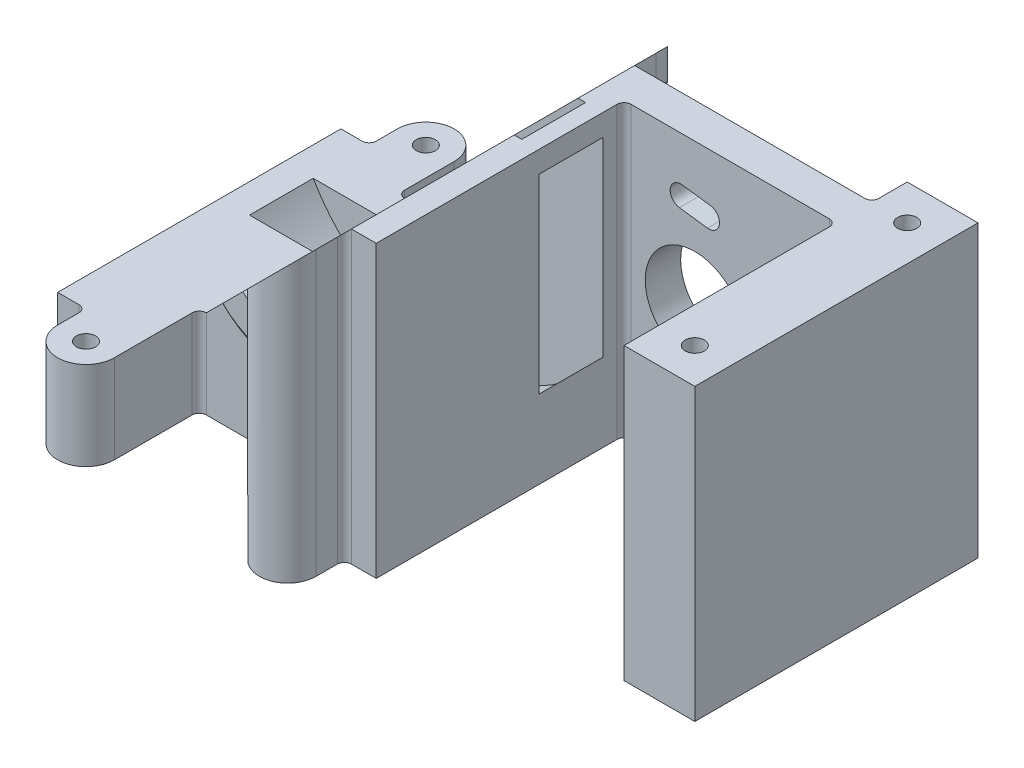
SolidWorks part; units mm, degrees
note: '?' marks a value the reader was unsure of.
ref_plane "Plan de face" through (0, 0, 0) normal (0, 0, 1) x (1, 0, 0)
ref_plane "Plan de dessus" through (0, 0, 0) normal (0, 1, 0) x (1, 0, 0)
ref_plane "Plan de droite" through (0, 0, 0) normal (1, 0, 0) x (0, 0, -1)
sketch "Esquisse1" plane through (0, 0, 0) normal (0, 1, 0) x (1, 0, 0)
  line L0 (-25, 20) -> (20, -20) construction
  line L1 (-30.3181, 0) -> (28.1212, 0) construction
  line L2 (0, 31.6907) -> (0, -43.6751) construction
  line L3 (16.5, 20) -> (49, 20)
  line L4 (15.5, 21) -> (15.5, 24)
  line L5 (7.5, 24) -> (7.5, 17)
  line L6 (-12, 16) -> (6.5, 16)
  line L7 (-13, 17) -> (-13, 24)
  line L8 (-21, 24) -> (-21, 21)
  line L9 (-22, 20) -> (-25, 20)
  line L30 (-25, 20) -> (-25, -20)
  line L31 (-22, -20) -> (-25, -20)
  line L32 (-21, -24) -> (-21, -21)
  line L33 (-13, -13) -> (-13, -24)
  line L35 (-12, -12) -> (6.5, -12)
  line L36 (7.5, -24) -> (7.5, -13)
  line L37 (15.5, -21) -> (15.5, -24)
  line L39 (20, -20) -> (16.5, -20)
  line L40 (20, 14) -> (20, -20)
  line L43 (49, 15) -> (21, 15)
  line L44 (50, -15) -> (50, 14)
  line L45 (60, -15) -> (50, -15)
  line L46 (60, 25) -> (60, -15)
  line L47 (50, 25) -> (60, 25)
  line L48 (50, 21) -> (50, 25)
  arc A0 (7.5, 24) -> (15.5, 24) centre (11.5, 24) cw
  arc A1 (-21, 24) -> (-13, 24) centre (-17, 24) cw
  arc A2 (-22, -20) -> (-21, -21) centre (-22, -21) cw
  arc A3 (-13, -13) -> (-12, -12) centre (-12, -13) cw
  arc A4 (7.5, -13) -> (6.5, -12) centre (6.5, -13) ccw
  arc A5 (15.5, -21) -> (16.5, -20) centre (16.5, -21) cw
  arc A6 (49, 15) -> (50, 14) centre (49, 14) cw
  arc A7 (-21, -24) -> (-13, -24) centre (-17, -24) ccw
  arc A8 (50, 21) -> (49, 20) centre (49, 21) cw
  arc A9 (7.5, -24) -> (15.5, -24) centre (11.5, -24) ccw
  arc A10 (20, 14) -> (21, 15) centre (21, 14) cw
  arc A11 (16.5, 20) -> (15.5, 21) centre (16.5, 21) cw
  arc A12 (7.5, 17) -> (6.5, 16) centre (6.5, 17) cw
  arc A13 (-12, 16) -> (-13, 17) centre (-12, 17) cw
  arc A14 (-21, 21) -> (-22, 20) centre (-22, 21) cw
  point P3 (-21, -20)
  point P21 (-25, 0)
  point P33 (-13, -12)
  point P36 (7.5, -12)
  point P43 (15.5, -20)
  point P52 (50, 20)
  point P57 (15.5, 20)
  point P60 (7.5, 16)
  point P63 (-13, 16)
  point P66 (-21, 20)
  dimension "D7" = 4
  dimension "D8" = 40
  dimension "D13" = 1
  dimension "D1" = 45
  dimension "D2" = 40
  dimension "D3" = 8
  dimension "D4" = 25
  dimension "D5" = 24
  dimension "D6" = 8.5
  dimension "D9" = 10
  dimension "D10" = 5
  dimension "D11" = 5
  dimension "D12" = 40
  dimension "D14" = 4
  dimension "D15" = 8
extrude "Boss.-Extru.1" add sketch "Esquisse1" along normal blind 41
sketch "Esquisse2" plane through (0, 0, 0) normal (0, 0, 1) x (1, 0, 0)
  line L0 (-25, 41) -> (16.5, 41)
  line L1 (16.5, 41) -> (4.0305, 28.5305)
  line L2 (-12, 12.5) -> (-25, 12.5)
  line L3 (-25, 41) -> (-25, 0) construction
  line L4 (-25, 12.5) -> (-25, 41)
  line L5 (-4.0305, 20.4695) -> (-12, 12.5)
  line L7 (0, -55) -> (0, 55) construction
  line L8 (55, 0) -> (-55, 0) construction
  arc A0 (4.0305, 28.5305) -> (-4.0305, 20.4695) centre (0, 24.5) cw
  dimension "D4" = 5.7
  dimension "D1" = 45
  dimension "D2" = 12.5
  dimension "D5" = 24.5
extrude "Enlèv. mat.-Extru.1" cut sketch "Esquisse2" against normal up to next and the other way up to next
ref_axis "Axe1" through (0, 24.5, 31.9307) along (0, 0, -1)?
ref_plane "Plan1" through (0, 0, -11) normal (0, 0, 1) x (1, 0, 0)
sketch "Esquisse3" plane through (0, 0, 0) normal (0, -1, 0) x (1, 0, 0)
  line L0 (-25, -20) -> (-25, 20) construction
  line L1 (50, 15) -> (60, 15) construction
  line L3 (-25, 20) -> (-22, 20) construction
  line L5 (-31.8576, 0) -> (68.3763, 0) construction
  circle A0 centre (-21, 16) radius 2.35
  circle A1 centre (16, 16) radius 2.35
  circle A2 centre (16, -16) radius 2.35
  circle A3 centre (-21, -16) radius 2.35
  circle A4 centre (55, 10) radius 2.35
  circle A5 centre (55, -20) radius 2.35
  point P21 (55, 15)
  dimension "D1" = 4.7
  dimension "D2" = 37
  dimension "D3" = 4
  dimension "D5" = 5
  dimension "D6" = 30
  dimension "D4" = 4
extrude "Enlèv. mat.-Extru.2" cut sketch "Esquisse3" against normal blind 10
sketch "Esquisse4" plane through (0, 0, -11) normal (0, 0, -1) x (-1, 0, 0)
  circle A0 centre (0, 24.5) radius 24.1
  dimension "D1" = 48.2
extrude "Enlèv. mat.-Extru.3" cut sketch "Esquisse4" against normal blind 8
sketch "Esquisse5" plane through (0, 0, -11) normal (0, 0, 1) x (1, 0, 0)
  circle A0 centre (0, 24.5) radius 24.1
  circle A1 centre (0, 24.5) radius 8.05
  circle A2 centre (0, 24.5) radius 24.1 construction
  dimension "D1" = 16.1
extrude "Enlèv. mat.-Extru.4" cut sketch "Esquisse5" against normal blind 1
sketch "Esquisse6" plane through (0, 0, -11) normal (0, 0, 1) x (1, 0, 0)
  circle A0 centre (0, 24.5) radius 7.5
  dimension "D1" = 15
extrude "Enlèv. mat.-Extru.5" cut sketch "Esquisse6" against normal blind 4
ref_plane "Plan2" through (0, 0, -2) normal (0, 0, 1) x (1, 0, 0)
mirror "Symétrie1" about plane through (0, 0, -2) normal (0, 0, 1) of "Enlèv. mat.-Extru.5"
sketch "Esquisse7" plane through (0, 0, -11) normal (0, 0, 1) x (1, 0, 0)
  circle A0 centre (0, 24.5) radius 15
  dimension "D1" = 30
extrude "Enlèv. mat.-Extru.7" cut sketch "Esquisse7" against normal up to surface (18 mm away)
sketch "Esquisse8" plane through (0, 0, 7) normal (0, 0, -1) x (-1, 0, 0)
  circle A0 centre (0, 24.5) radius 8.05
  circle A1 centre (0, 24.5) radius 15
  arc A2 (-5.6922, 30.1922) -> (5.6922, 18.8078) centre (0, 24.5) ccw construction
  arc A4 (-10.6066, 35.1066) -> (10.6066, 13.8934) centre (0, 24.5) ccw construction
extrude "Enlèv. mat.-Extru.8" cut sketch "Esquisse8" against normal blind 1
fillet "Congé2" radius 2 3 edges at (5.6922, 18.8078, -12) (5.6922, 18.8078, 8) (10.6066, 13.8934, -3)
sketch "Esquisse9" plane through (0, 0, -16) normal (0, 0, -1) x (-1, 0, 0)
  line L0 (4.0305, 20.4695) -> (12, 12.5) construction
  line L1 (-7.5, 32) -> (-15.5, 40) construction
  line L2 (-6.5, 31) -> (-4.0305, 28.5305) construction
  line L3 (-7.9196, 32.4196) -> (-4.0305, 28.5305)
  line L4 (7.9196, 16.5804) -> (4.0305, 20.4695)
  line L5 (4.0305, 20.4695) -> (4.0647, 20.454)
  arc A0 (7.9196, 16.5804) -> (-7.9196, 32.4196) centre (0, 24.5) cw
  arc A1 (4.0305, 20.4695) -> (-4.0305, 28.5305) centre (0, 24.5) cw
  line M2 (12, 12.5) -> (4.0305, 20.4695)
  arc M3 (4.0305, 20.4695) -> (-4.0305, 28.5305) centre (0, 24.5) cw
  line M4 (-4.0305, 28.5305) -> (-6.5, 31)
  line M5 (-6.5, 31) -> (-6.5, 0)
  dimension "D1" = 5.5
extrude "Boss.-Extru.2" add sketch "Esquisse9" along normal blind 1.75 contours A0 M2 M3 M4 M5
chamfer "Chanfrein1" distance 1.75 distance2 2.5 1 edges at (-0.9298, 13.3387, -16)
mirror "Symétrie3" about plane through (0, 0, -2) normal (0, 0, 1) of "Boss.-Extru.2"
chamfer "Chanfrein2" distance 2.5 distance2 1.75 1 edges at (-0.9298, 13.3387, 12)
sketch "Esquisse10" plane through (0, 41, 0) normal (0, 1, 0) x (1, 0, 0)
  circle A0 centre (11.5, 24) radius 1.35
  circle A1 centre (11.5, -24) radius 1.35
  circle A2 centre (55, 20) radius 1.35
  circle A3 centre (55, -10) radius 1.35
  circle A4 centre (11.5, 16.8) radius 1.35
  circle A5 centre (11.5, -16.8) radius 1.35
  dimension "D1" = 2.7
extrude "Enlèv. mat.-Extru.9" cut sketch "Esquisse10" against normal blind 12
sketch "Esquisse11" plane through (0, 12.5, 0) normal (0, 1, 0) x (1, 0, 0)
  circle A0 centre (-17, 24) radius 1.35
  circle A1 centre (-17, -24) radius 1.35
  dimension "D1" = 2.7
extrude "Enlèv. mat.-Extru.10" cut sketch "Esquisse11" against normal blind 7
sketch "Esquisse12" plane through (0, 0, -20) normal (0, 0, 1) x (1, 0, 0)
  line L3 (16.5, 41) -> (16.5, 0) construction
  circle A0 centre (30, 20.5) radius 7
  point P7 (16.5, 20.5)
  dimension "D1" = 14
  dimension "D2" = 30
extrude "Enlèv. mat.-Extru.12" cut sketch "Esquisse12" along normal up to next
sketch "Esquisse14" plane through (0, 0, -20) normal (0, 0, -1) x (-1, 0, 0)
  circle A0 centre (-30, 20.5) radius 21
  circle A1 centre (-30, 20.5) radius 7 construction
  dimension "D1" = 42
extrude "Enlèv. mat.-Extru.13" cut sketch "Esquisse14" along normal up to next
fillet "Congé6" radius 1 2 edges at (9, 20.5, -20) (51, 20.5, -20)
ref_axis "Axe2" through (30, 20.5, 15.8583) along (0, 0, -1)?
ref_plane "Plan3" through (3.2096, 24.0721, 0) normal (0.1322, 0.9912, 0) x (0.9912, -0.1322, 0)
sketch "Esquisse15" plane through (0, 0, -15) normal (0, 0, 1) x (1, 0, 0)
  line L0 (28.0175, 33.2643) -> (31.9825, 32.7357) construction
  line L1 (28.2158, 34.7512) -> (32.1807, 34.2225)
  line L2 (27.8193, 31.7775) -> (31.7842, 31.2488)
  line L3 (21.2319, 21.6691) -> (-14.8126, 26.475) construction
  arc A0 (28.2158, 34.7512) -> (27.8193, 31.7775) centre (28.0175, 33.2643) ccw
  arc A1 (31.7842, 31.2488) -> (32.1807, 34.2225) centre (31.9825, 32.7357) ccw
  point P2 (30, 33)
  dimension "D3" = 12.5
  dimension "D1" = 4
  dimension "D2" = 3
extrude "Enlèv. mat.-Extru.14" cut sketch "Esquisse15" against normal up to next
ref_plane "Plan4" through (0, 20.5, 0) normal (0, 1, 0) x (1, 0, 0)
pattern_circular "Répétition circulaire2" count 2 over 360 about axis through (30, 20.5, 0) along (0, 0, 1) of "Enlèv. mat.-Extru.14"
chamfer "Chanfrein3" distance 1.5 angle 45 2 edges at (4.0305, 20.4695, -17.75) (4.0305, 20.4695, 13.75)
